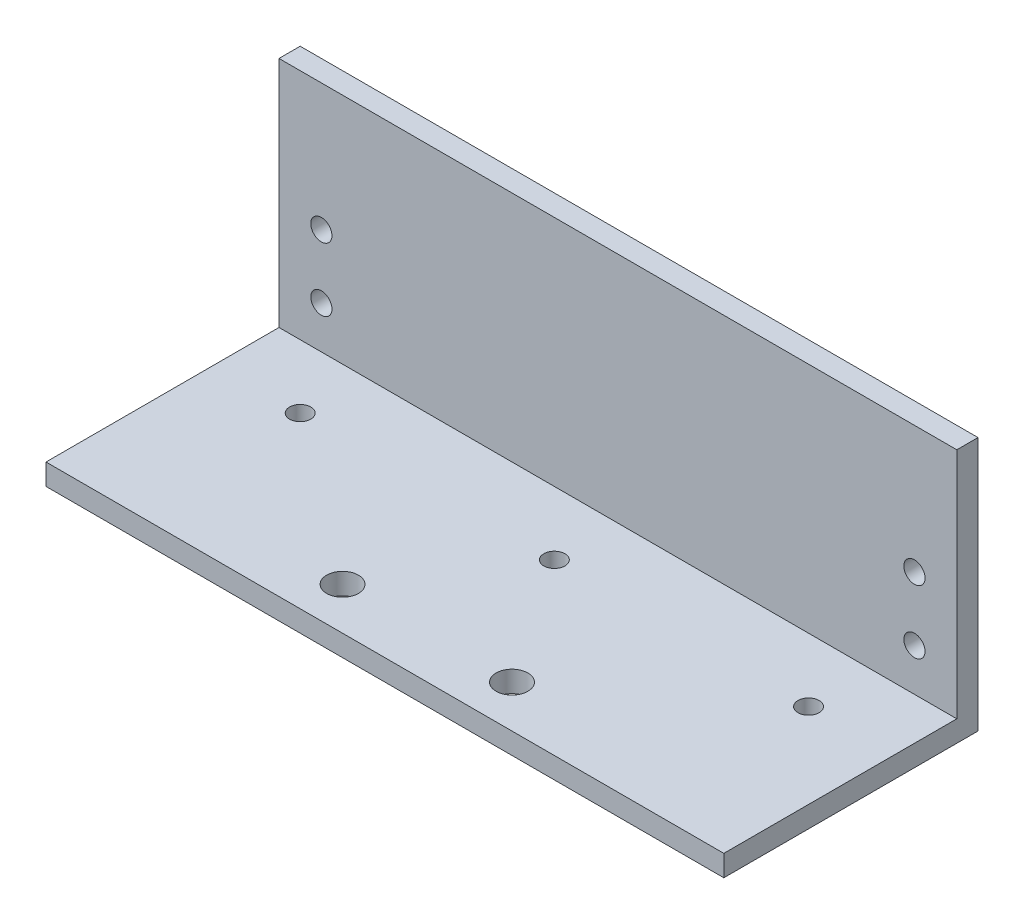
SolidWorks part; units mm, degrees
material "6061 Alloy"
ref_plane "Front Plane" through (0, 0, 0) normal (0, 0, 1) x (1, 0, 0)
ref_plane "Top Plane" through (0, 0, 0) normal (0, 1, 0) x (1, 0, 0)
ref_plane "Right Plane" through (0, 0, 0) normal (1, 0, 0) x (0, 0, -1)
sketch "Sketch2" plane through (0, 0, 0) normal (1, 0, 0) x (0, 0, -1)
  line L1 (0, 0) -> (76.2, 0)
  line L2 (0, 0) -> (0, 76.2)
  line L3 (0, 76.2) -> (76.2, 76.2)
  line L4 (76.2, 0) -> (76.2, 76.2)
  line L5 (0, 76.2) -> (69.85, 76.2)
  line L6 (0, 76.2) -> (0, 6.35)
  line L7 (0, 6.35) -> (69.85, 6.35)
  line L8 (69.85, 76.2) -> (69.85, 6.35)
  dimension "D1" = 76.2
  dimension "D2" = 76.2
  dimension "D3" = 6.35
  dimension "D4" = 6.35
extrude "Boss-Extrude2" add sketch "Sketch2" along normal blind 203.2 contours L3 L8 L7 L2 L1 L4 region at (0, 3.175, -1.0776)
sketch "Sketch4" plane through (0, 0, -76.2) normal (0, 0, -1) x (-1, 0, 0)
  line L0 (-203.2, 0) -> (0, 0) construction
  line L1 (-203.2, 0) -> (-203.2, 76.2) construction
  circle A0 centre (-190.5, 19.05) radius 3.175
  circle A1 centre (-190.5, 38.1) radius 3.175
  circle A2 centre (-12.7, 19.05) radius 3.175
  circle A3 centre (-12.7, 38.1) radius 3.175
  dimension "D1" = 19.05
  dimension "D2" = 12.7
  dimension "D3" = 38.1
  dimension "D4" = 190.5
  dimension "D5" = 38.1
  dimension "D6" = 190.5
extrude "Cut-Extrude1" cut sketch "Sketch4" against normal blind 71.628
sketch "Sketch5" plane through (0, 6.35, 0) normal (0, 1, 0) x (1, 0, 0)
  line L0 (0, 0) -> (0, 69.85) construction
  line L1 (203.2, 0) -> (0, 0) construction
  circle A0 centre (25.4, 50.8) radius 3.175
  circle A1 centre (177.8, 50.8) radius 3.175
  circle A2 centre (101.6, 50.8) radius 3.175
  dimension "D1" = 177.8
  dimension "D2" = 6.35
  dimension "D3" = 50.8
  dimension "D4" = 101.6
  dimension "D5" = 50.8
  dimension "D6" = 50.8
  dimension "D7" = 25.4
extrude "Cut-Extrude2" cut sketch "Sketch5" against normal blind 244.602
sketch "Sketch6" plane through (0, 6.35, 0) normal (0, 1, 0) x (1, 0, 0)
  line L0 (203.2, 0) -> (0, 0) construction
  circle A0 centre (76.2, 12.7) radius 4.7625
  circle A1 centre (127, 12.7) radius 4.7625
  circle A2 centre (101.6, 50.8) radius 3.175 construction
  dimension "D1" = 12.7
  dimension "D2" = 0
  dimension "D3" = 25.4
  dimension "D4" = 25.4
extrude "Cut-Extrude3" cut sketch "Sketch6" against normal blind 28.702
